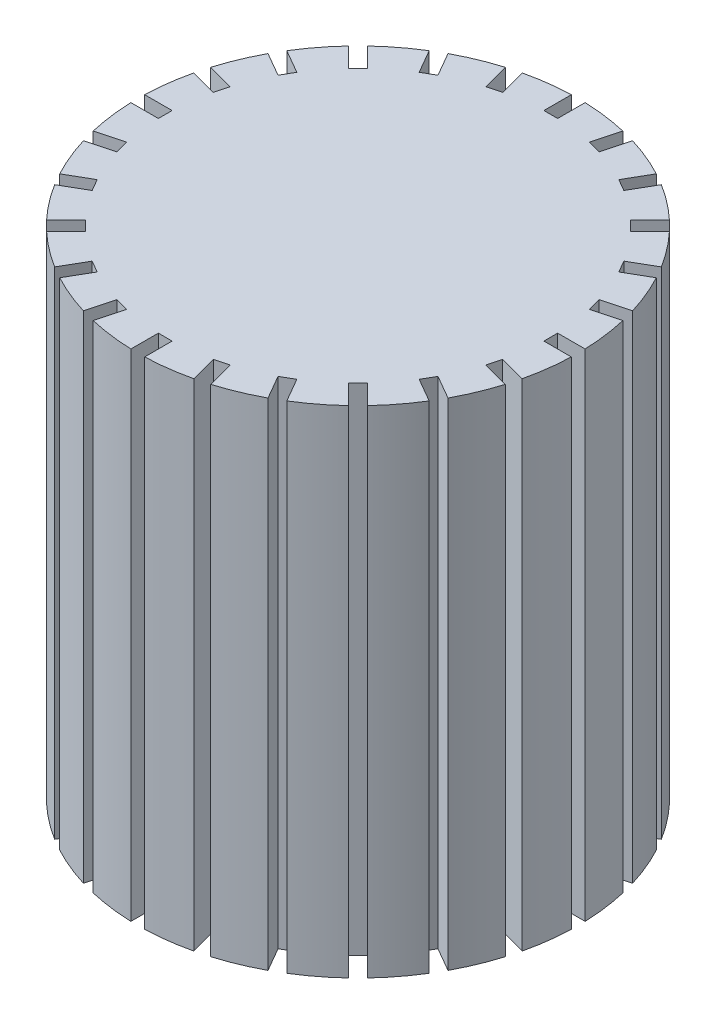
SolidWorks part; units mm, degrees
material "ABS"
ref_plane "Front Plane" through (0, 0, 0) normal (0, 0, 1) x (1, 0, 0)
ref_plane "Top Plane" through (0, 0, 0) normal (0, 1, 0) x (1, 0, 0)
ref_plane "Right Plane" through (0, 0, 0) normal (1, 0, 0) x (0, 0, -1)
sketch "Sketch1" plane through (0, 0, 0) normal (0, 1, 0) x (1, 0, 0)
  circle A0 centre (0, 0) radius 4
  circle A1 centre (0, 0) radius 2.375
  dimension "D1" = 8
  dimension "D2" = 4.75
extrude "Boss-Extrude1" add sketch "Sketch1" along normal blind 5 contours A1 | A0 A1 region at (-3.8869, 0, 0) region at (0, 0, 0)
extrude "Boss-Extrude2" add sketch "Sketch1<3>" against normal blind 4 contours A0 A1 region at (-3.8869, 0, 0)
sketch "Sketch1<3>" plane through (0, 0, 0) normal (0, 1, 0) x (1, 0, 0) same geometry as "Sketch1"
sketch "Sketch2" plane through (0, -4, 0) normal (0, -1, 0) x (1, 0, 0)
  line L1 (-0.125, 4) -> (0.125, 4)
  line L2 (-0.125, 4) -> (-0.125, 3.5)
  line L3 (-0.125, 3.5) -> (0.125, 3.5)
  line L4 (0.125, 4) -> (0.125, 3.5)
  point P4 (0, 4)
  point P260 (0, 0)
  dimension "D1" = 3.5
  dimension "D2" = 0.25
  dimension "D3" = 0.5
extrude "Cut-Extrude1" cut sketch "Sketch2" against normal through all
pattern_circular "CirPattern1" count 24 every 15 about axis through (0, -4, 0) along (0, 1, 0) of "Cut-Extrude1"
